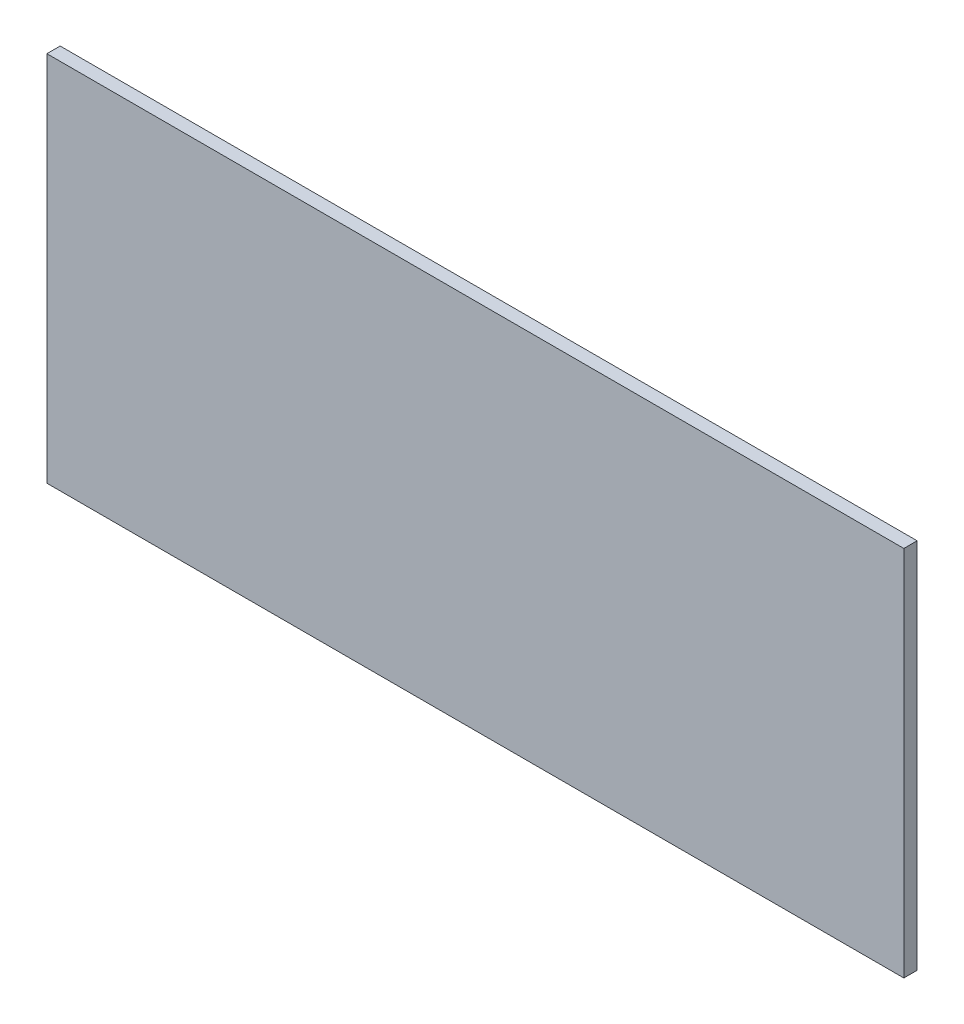
SolidWorks part; units mm, degrees
ref_plane "Front Plane" through (0, 0, 0) normal (0, 0, 1) x (1, 0, 0)
ref_plane "Top Plane" through (0, 0, 0) normal (0, 1, 0) x (1, 0, 0)
ref_plane "Right Plane" through (0, 0, 0) normal (1, 0, 0) x (0, 0, -1)
sketch "Sketch1" plane through (0, 0, 0) normal (0, 0, 1) x (1, 0, 0)
  line L1 (0, 0) -> (409.575, 0)
  line L2 (0, 0) -> (0, 177.8)
  line L3 (0, 177.8) -> (409.575, 177.8)
  line L4 (409.575, 0) -> (409.575, 177.8)
  dimension "D1" = 177.8
  dimension "D2" = 409.575
extrude "Boss-Extrude1" add sketch "Sketch1" along normal blind 6.35
